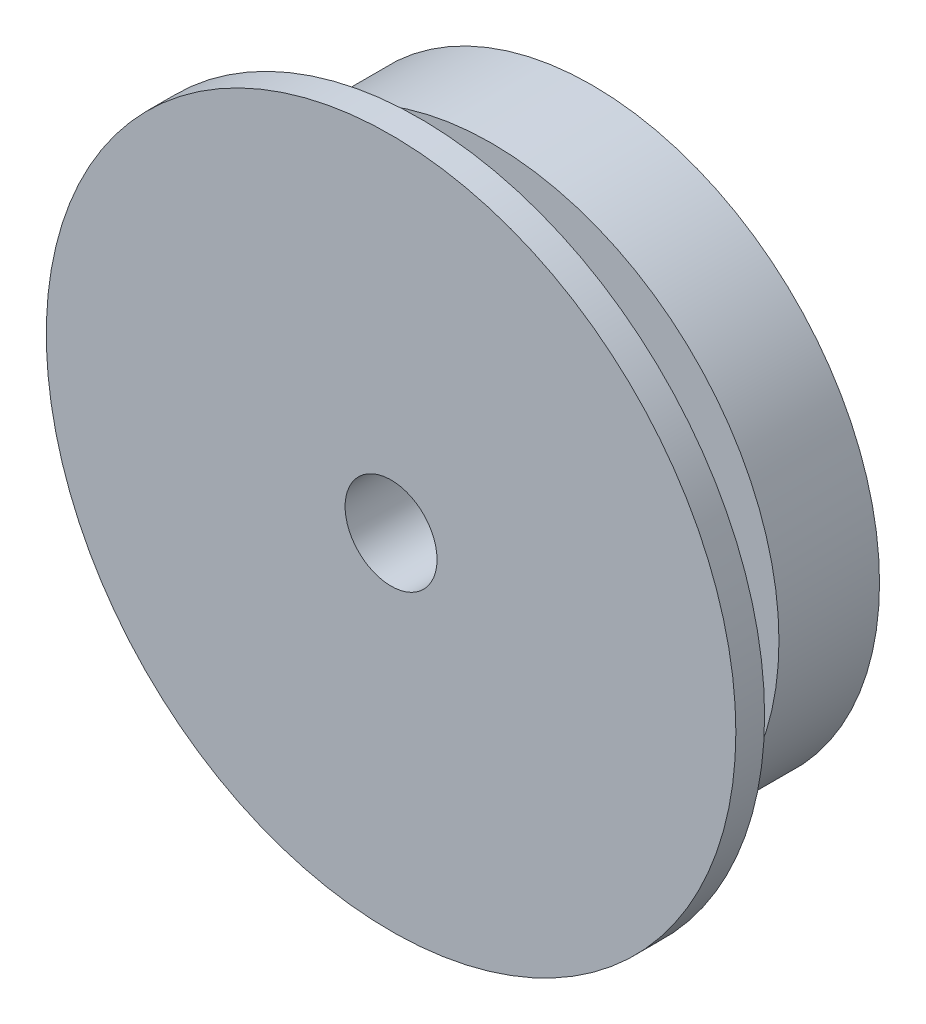
SolidWorks part; units mm, degrees
material "Resina de melamina"
ref_plane "Alzado" through (0, 0, 0) normal (0, 0, 1) x (1, 0, 0)
ref_plane "Planta" through (0, 0, 0) normal (0, 1, 0) x (1, 0, 0)
ref_plane "Vista lateral" through (0, 0, 0) normal (1, 0, 0) x (0, 0, -1)
sketch "Croquis1" plane through (0, 0, 0) normal (0, 0, 1) x (1, 0, 0)
  circle A0 centre (0, 0) radius 11
  circle A1 centre (0, 0) radius 25
  dimension "D1" = 50
  dimension "D2" = 22
extrude "Saliente-Extruir1" add sketch "Croquis1" along normal blind 19
ref_plane "Plano1" through (0, 0, 6) normal (0, 0, -1) x (-1, 0, 0)
sketch "Croquis3" plane through (0, 0, 6) normal (0, 0, -1) x (-1, 0, 0)
  circle A0 centre (0, 0) radius 11
  circle A1 centre (0, 0) radius 9.5
  dimension "D1" = 19
extrude "Saliente-Extruir2" add sketch "Croquis3" against normal through all
sketch "Croquis4" plane through (0, 0, 19) normal (0, 0, 1) x (1, 0, 0)
  circle A0 centre (0, 0) radius 11
  circle A1 centre (0, 0) radius 4
  dimension "D1" = 8
extrude "Saliente-Extruir3" add sketch "Croquis4" against normal blind 2
sketch "Croquis5" plane through (0, 0, 19) normal (0, 0, 1) x (1, 0, 0)
  circle A0 centre (0, 0) radius 25
  circle A1 centre (0, 0) radius 30
  dimension "D1" = 60
extrude "Saliente-Extruir4" add sketch "Croquis5" against normal blind 2.5
ref_plane "Plano2" through (0, 0, 14.25) normal (0, 0, -1) x (-1, 0, 0)
sketch "Croquis6" plane through (0, 0, 14.25) normal (0, 0, -1) x (-1, 0, 0)
  circle A1 centre (0, 0) radius 25
  circle A2 centre (0, 0) radius 19
  dimension "D1" = 38
extrude "Cortar-Extruir1" cut sketch "Croquis6" along normal blind 4
sketch "Croquis7" plane through (0, 0, 0) normal (0, 0, -1) x (-1, 0, 0)
  circle A0 centre (0, 0) radius 11
  circle A1 centre (0, 0) radius 4
extrude "Saliente-Extruir5" add sketch "Croquis7" against normal through all
sketch "Croquis8" plane through (0, 0, 0) normal (0, 0, -1) x (-1, 0, 0)
  circle A0 centre (0, 0) radius 4
  circle A1 centre (0, 0) radius 6.1
  dimension "D1" = 12.2
extrude "Saliente-Extruir6" add sketch "Croquis8" along normal blind 2
sketch "Croquis9" plane through (0, 0, 0) normal (0, 0, -1) x (-1, 0, 0)
  circle A0 centre (0, 0) radius 25
  circle A1 centre (0, 0) radius 15
  dimension "D1" = 30
extrude "Cortar-Extruir2" cut sketch "Croquis9" against normal blind 1.5
